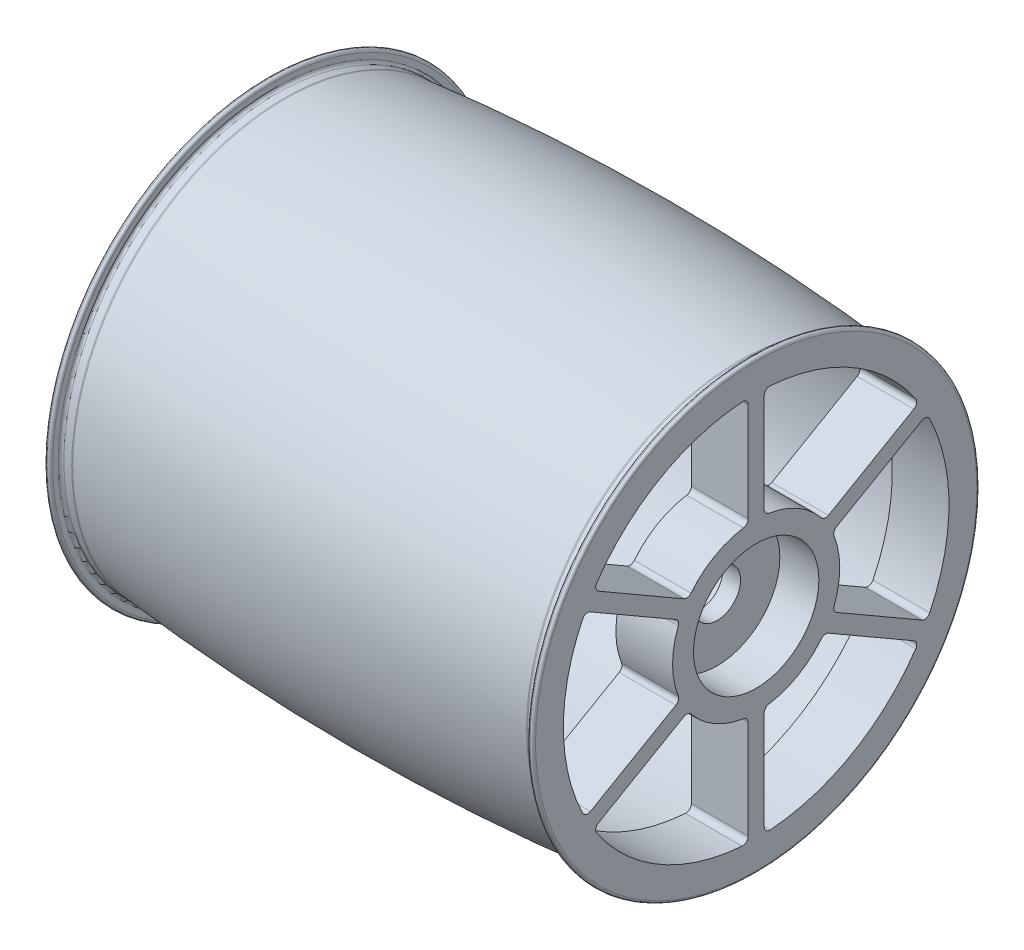
SolidWorks part; units mm, degrees
ref_plane "Front Plane" through (0, 0, 0) normal (0, 0, 1) x (1, 0, 0)
ref_plane "Top Plane" through (0, 0, 0) normal (0, 1, 0) x (1, 0, 0)
ref_plane "Right Plane" through (0, 0, 0) normal (1, 0, 0) x (0, 0, -1)
sketch "Sketch1" plane through (0, 0, 0) normal (0, 0, 1) x (1, 0, 0)
  line L0 (-40.815, 0) -> (40.815, 0) construction
  line L1 (-40.815, 0) -> (-40.815, 38.1) construction
  line L2 (40.815, 0) -> (40.815, 38.1) construction
  line L3 (0, 0) -> (0, 40.1) construction
  line L4 (-40.815, 38.1) -> (-42.815, 38.1)
  line L5 (40.815, 38.1) -> (42.815, 38.1)
  line L9 (-42.815, 38.1) -> (-42.815, 40.1)
  line L10 (-42.815, 40.1) -> (-43.815, 40.1)
  line L11 (-43.815, 40.1) -> (-43.815, 0)
  line L12 (-43.815, 0) -> (-33.64, 0)
  line L14 (42.815, 38.1) -> (42.815, 40.1)
  line L15 (42.815, 40.1) -> (43.815, 40.1)
  line L16 (43.815, 40.1) -> (43.815, 0)
  line L17 (43.815, 0) -> (33.64, 0)
  line L19 (-33.64, 0) -> (-33.64, 37.7391)
  line L20 (33.64, 0) -> (33.64, 37.7391)
  arc A0 (-40.815, 38.1) -> (40.815, 38.1) centre (0, -377.3661) cw
  arc A1 (-33.64, 37.7391) -> (33.64, 37.7391) centre (0, -377.3661) cw
  dimension "D3" = 1
  dimension "D1" = 38.1
  dimension "D4" = 2
  dimension "D8" = 1
  dimension "D9" = 40.1
  dimension "D10" = 10.175
  dimension "D2" = 87.63
revolve "Revolve2" add sketch "Sketch1" angle 360 about L0
fillet "Fillet2" radius 2 4 edges at (40.815, 0, 38.1) (-40.815, 0, 38.1) (33.64, 0, 37.7391) (-33.64, 0, 37.7391)
fillet "Fillet1" radius 0.5 6 edges at (43.815, 0, 40.1) (42.815, 0, 40.1) (42.815, 0, 38.1) (-42.815, 0, 38.1) (-42.815, 0, 40.1) (-43.815, 0, 40.1)
sketch "Sketch2" plane through (-43.815, 0, 0) normal (-1, 0, 0) x (0, 0, 1)
  line L0 (0, 0) -> (13.6518, 0) construction
  line L1 (14.4156, 6.6562) -> (29.7431, 15.5055)
  line L2 (13.6518, 6.2152) -> (13.6518, -6.2152) construction
  line L3 (14.4156, -6.6562) -> (29.7431, -15.5055)
  line L4 (30.6601, 16.0349) -> (30.6601, -16.0349) construction
  line L5 (2.8868, 0) -> (13.6518, 6.2152) construction
  line L6 (2.8868, 0) -> (1.4434, 2.5) construction
  line L7 (1.4434, 2.5) -> (-1.4434, 2.5) construction
  line L8 (-1.4434, 2.5) -> (-2.8868, 0) construction
  line L9 (-2.8868, 0) -> (-1.4434, -2.5) construction
  line L10 (-1.4434, -2.5) -> (1.4434, -2.5) construction
  line L11 (1.4434, -2.5) -> (2.8868, 0) construction
  line L12 (13.6518, 0) -> (30.6601, 0) construction
  line L13 (13.6518, -6.2152) -> (2.8868, 0) construction
  line L14 (12.9722, -9.1562) -> (28.2997, -18.0055)
  line L15 (1.4434, -15.8123) -> (1.4434, -33.511)
  line L16 (-1.4434, -15.8123) -> (-1.4434, -33.511)
  line L17 (-12.9722, -9.1562) -> (-28.2997, -18.0055)
  line L18 (-14.4156, -6.6562) -> (-29.7431, -15.5055)
  line L19 (-14.4156, 6.6562) -> (-29.7431, 15.5055)
  line L20 (-12.9722, 9.1562) -> (-28.2997, 18.0055)
  line L21 (-1.4434, 15.8123) -> (-1.4434, 33.511)
  line L22 (1.4434, 15.8123) -> (1.4434, 33.511)
  line L23 (12.9722, 9.1562) -> (28.2997, 18.0055)
  arc A0 (31.1432, 15.0752) -> (31.1432, -15.0752) centre (0, 0) cw
  circle A1 centre (0, 0) radius 39.6 construction
  circle A2 centre (0, 0) radius 2.5 construction
  arc A3 (13.9833, 5.4283) -> (13.9833, -5.4283) centre (0, 0) cw
  arc A4 (13.9833, -5.4283) -> (14.4156, -6.6562) centre (14.9156, -5.7901) ccw
  arc A5 (14.4156, 6.6562) -> (13.9833, 5.4283) centre (14.9156, 5.7901) ccw
  arc A6 (29.7431, -15.5055) -> (31.1432, -15.0752) centre (30.2431, -14.6395) ccw
  arc A7 (31.1432, 15.0752) -> (29.7431, 15.5055) centre (30.2431, 14.6395) ccw
  arc A8 (28.6271, -19.4332) -> (28.2997, -18.0055) centre (27.7997, -18.8715) ccw
  arc A9 (28.6271, -19.4332) -> (2.5161, -34.5084) centre (0, 0) cw
  arc A10 (1.4434, -33.511) -> (2.5161, -34.5084) centre (2.4434, -33.511) ccw
  arc A11 (2.2907, -14.8241) -> (1.4434, -15.8123) centre (2.4434, -15.8123) ccw
  arc A12 (11.6927, -9.3958) -> (2.2907, -14.8241) centre (0, 0) cw
  arc A13 (12.9722, -9.1562) -> (11.6927, -9.3958) centre (12.4722, -10.0222) ccw
  arc A14 (-2.5161, -34.5084) -> (-1.4434, -33.511) centre (-2.4434, -33.511) ccw
  arc A15 (-2.5161, -34.5084) -> (-28.6271, -19.4332) centre (0, 0) cw
  arc A16 (-28.2997, -18.0055) -> (-28.6271, -19.4332) centre (-27.7997, -18.8715) ccw
  arc A17 (-11.6927, -9.3958) -> (-12.9722, -9.1562) centre (-12.4722, -10.0222) ccw
  arc A18 (-2.2907, -14.8241) -> (-11.6927, -9.3958) centre (0, 0) cw
  arc A19 (-1.4434, -15.8123) -> (-2.2907, -14.8241) centre (-2.4434, -15.8123) ccw
  arc A20 (-31.1432, -15.0752) -> (-29.7431, -15.5055) centre (-30.2431, -14.6395) ccw
  arc A21 (-31.1432, -15.0752) -> (-31.1432, 15.0752) centre (0, 0) cw
  arc A22 (-29.7431, 15.5055) -> (-31.1432, 15.0752) centre (-30.2431, 14.6395) ccw
  arc A23 (-13.9833, 5.4283) -> (-14.4156, 6.6562) centre (-14.9156, 5.7901) ccw
  arc A24 (-13.9833, -5.4283) -> (-13.9833, 5.4283) centre (0, 0) cw
  arc A25 (-14.4156, -6.6562) -> (-13.9833, -5.4283) centre (-14.9156, -5.7901) ccw
  arc A26 (-28.6271, 19.4332) -> (-28.2997, 18.0055) centre (-27.7997, 18.8715) ccw
  arc A27 (-28.6271, 19.4332) -> (-2.5161, 34.5084) centre (0, 0) cw
  arc A28 (-1.4434, 33.511) -> (-2.5161, 34.5084) centre (-2.4434, 33.511) ccw
  arc A29 (-2.2907, 14.8241) -> (-1.4434, 15.8123) centre (-2.4434, 15.8123) ccw
  arc A30 (-11.6927, 9.3958) -> (-2.2907, 14.8241) centre (0, 0) cw
  arc A31 (-12.9722, 9.1562) -> (-11.6927, 9.3958) centre (-12.4722, 10.0222) ccw
  arc A32 (2.5161, 34.5084) -> (1.4434, 33.511) centre (2.4434, 33.511) ccw
  arc A33 (2.5161, 34.5084) -> (28.6271, 19.4332) centre (0, 0) cw
  arc A34 (28.2997, 18.0055) -> (28.6271, 19.4332) centre (27.7997, 18.8715) ccw
  arc A35 (11.6927, 9.3958) -> (12.9722, 9.1562) centre (12.4722, 10.0222) ccw
  arc A36 (2.2907, 14.8241) -> (11.6927, 9.3958) centre (0, 0) cw
  arc A37 (1.4434, 15.8123) -> (2.2907, 14.8241) centre (2.4434, 15.8123) ccw
  point P92 (0, 0)
  dimension "D5" = 5
  dimension "D2" = 15
  dimension "D3" = 1
  dimension "D4" = 5
  dimension "D1" = 30
  dimension "D6" = 6
extrude "Cut-Extrude2" cut sketch "Sketch2" against normal through all
sketch "Sketch7" plane through (43.815, 0, 0) normal (1, 0, 0) x (0, 0, -1)
  circle A0 centre (0, 0) radius 4.2
  dimension "D1" = 8.4
extrude "Cut-Extrude5" cut sketch "Sketch7" against normal through all both and the other way through all
sketch "Sketch8" plane through (43.815, 0, 0) normal (1, 0, 0) x (0, 0, -1)
  circle A0 centre (0, 0) radius 11.25
  dimension "D1" = 22.5
extrude "Cut-Extrude6" cut sketch "Sketch8" against normal blind 7
ref_plane "Plane1" through (0, 0, 0) normal (1, 0, 0) x (0, -1, 0)
mirror "Mirror1" about plane through (0, 0, 0) normal (1, 0, 0) of "Cut-Extrude6"
equation "\"SpokeWidth\"= 5"
equation "\"D5@Sketch2\" = \"SpokeWidth\""
equation "\"HubDiameter\"= 30"
equation "\"D2@Sketch2\"=\"HubDiameter\"/2"
equation "\"PulleyDiameter\"= 3in"
equation "\"D1@Sketch1\"=\"PulleyDiameter\"/2"
equation "\"D9@Sketch1\"=(\"PulleyDiameter\"/2) + 2"
equation "\"PulleyWidth\"= 3.45in"
equation "\"RimWidth\"= 5"
equation "\"D4@Sketch2\"=\"RimWidth\""
equation "\"D2@Sketch1\"=\"PulleyWidth\""
